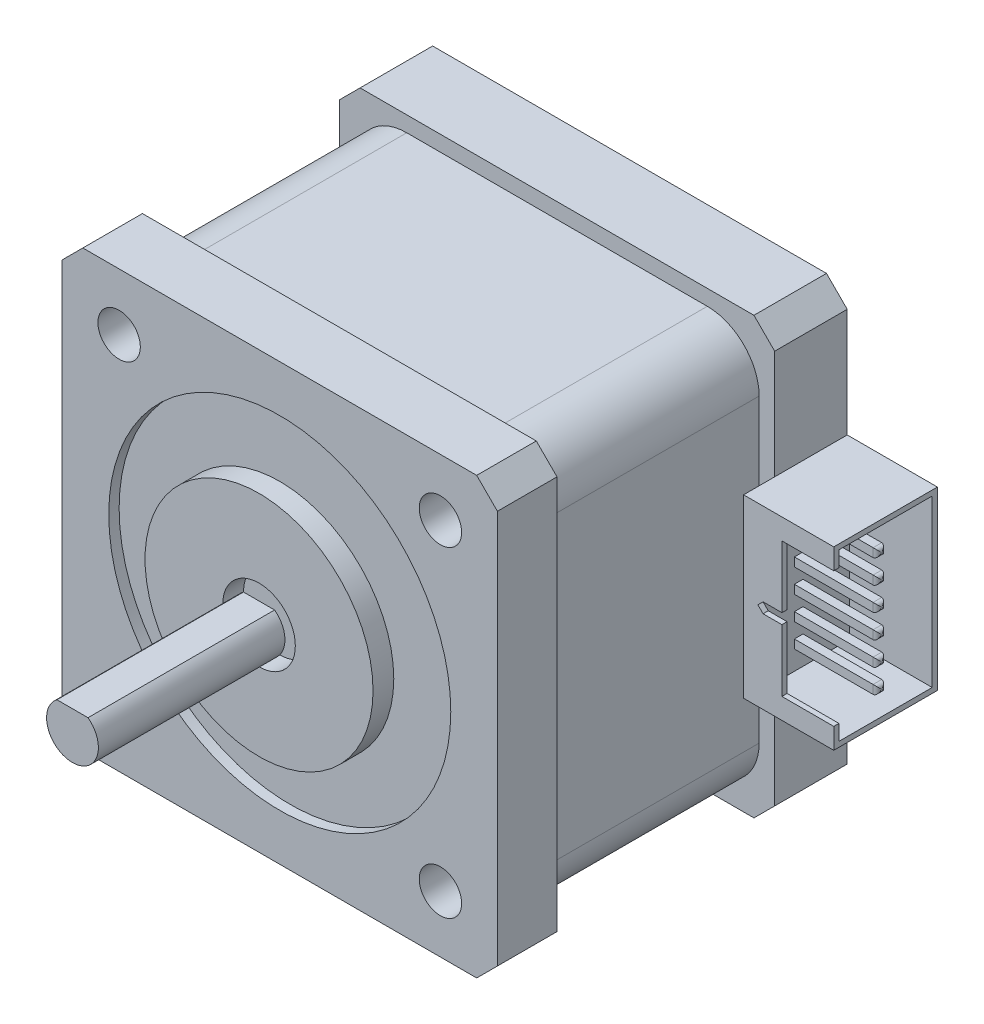
SolidWorks part; units mm, degrees
ref_plane "Alzado" through (0, 0, 0) normal (0, 0, 1) x (1, 0, 0)
ref_plane "Planta" through (0, 0, 0) normal (0, 1, 0) x (1, 0, 0)
ref_plane "Vista lateral" through (0, 0, 0) normal (1, 0, 0) x (0, 0, -1)
sketch "Croquis3" plane through (0, 0, 0) normal (0, 0, 1) x (1, 0, 0)
  line L0 (-1.5, 2) -> (1.5, 2)
  arc A0 (-1.5, 2) -> (1.5, 2) centre (0, 0) ccw
  dimension "D1" = 5
  dimension "D2" = 2
extrude "Saliente-Extruir1" add sketch "Croquis3" along normal blind 53.75
sketch "Croquis5" plane through (0, 0, 0) normal (0, 0, 1) x (1, 0, 0)
  line L1 (-21, 21) -> (21, 21)
  line L2 (-21, 21) -> (-21, -21)
  line L3 (-21, -21) -> (21, -21)
  line L4 (21, 21) -> (21, -21)
  line L5 (29.7, -8.5) -> (21, -8.5)
  line L6 (29.7, -8.5) -> (29.7, 8.5)
  line L7 (29.7, 8.5) -> (21, 8.5)
  line L8 (21, -8.5) -> (21, 8.5)
  dimension "D1" = 42
  dimension "D2" = 42
  dimension "D3" = 17
  dimension "D4" = 8.7
  dimension "D5" = 12.5
extrude "Saliente-Extruir2" add sketch "Croquis5" along normal blind 7 contours L4 L1 L2 L3 region at (0, 0, 0)
extrude "Saliente-Extruir3" add sketch "Croquis5<3>" along normal blind 10 contours L6 L7 L4 L5 region at (25.35, 0, 0)
sketch "Croquis5<3>" plane through (0, 0, 0) normal (0, 0, 1) x (1, 0, 0) same geometry as "Croquis5"
sketch "Croquis6" plane through (0, 0, 7) normal (0, 0, 1) x (1, 0, 0)
  line L1 (-19.5, 19.5) -> (19.5, 19.5)
  line L2 (-19.5, 19.5) -> (-19.5, -19.5)
  line L3 (-19.5, -19.5) -> (19.5, -19.5)
  line L4 (19.5, 19.5) -> (19.5, -19.5)
  point P4 (12.5866, -9.7505)
  point P5 (12.9433, -9.2154)
  point P8 (0, -19.5)
  point P9 (-19.5, 0)
  dimension "D1" = 39
extrude "Saliente-Extruir4" add sketch "Croquis6" along normal blind 21
sketch "Croquis7" plane through (0, 0, 28) normal (0, 0, 1) x (1, 0, 0)
  line L1 (-21, 21) -> (21, 21)
  line L2 (-21, 21) -> (-21, -21)
  line L3 (-21, -21) -> (21, -21)
  line L4 (21, 21) -> (21, -21)
extrude "Saliente-Extruir5" add sketch "Croquis7" along normal blind 5.75
sketch "Croquis8" plane through (0, 0, 33.75) normal (0, 0, 1) x (1, 0, 0)
  circle A0 centre (0, 0) radius 11
  dimension "D1" = 22
extrude "Saliente-Extruir6" add sketch "Croquis8" along normal blind 2
sketch "Croquis9" plane through (0, 0, 33.75) normal (0, 0, 1) x (1, 0, 0)
  circle A0 centre (0, 0) radius 16.5
  dimension "D1" = 33
extrude "Cortar-Extruir3" cut sketch "Croquis9" against normal blind 1
sketch "Croquis10" plane through (0, 0, 35.75) normal (0, 0, 1) x (1, 0, 0)
  circle A0 centre (0, 0) radius 3.5
  dimension "D1" = 7
extrude "Cortar-Extruir4" cut sketch "Croquis10" against normal blind 3
chamfer "Chaflán1" distance 2 angle 45 8 edges at (21, -21, 3.5) (21, -21, 30.875) (21, 21, 30.875) (21, 21, 3.5) (-21, 21, 30.875) (-21, 21, 3.5) (-21, -21, 3.5) (-21, -21, 30.875)
fillet "Redondeo1" radius 5 4 edges at (19.5, -19.5, 17.5) (-19.5, -19.5, 17.5) (-19.5, 19.5, 17.5) (19.5, 19.5, 17.5)
sketch "Croquis11" plane through (0, 0, 33.75) normal (0, 0, 1) x (1, 0, 0)
  line L0 (19, 21) -> (-19, 21) construction
  line L1 (-21, 19) -> (-21, -19) construction
  circle A0 centre (-15.5, 15.5) radius 2.0458
  circle A1 centre (15.5, 15.5) radius 2.0458
  circle A2 centre (15.5, -15.5) radius 2.0458
  circle A3 centre (-15.5, -15.5) radius 2.0458
  dimension "D1" = 5.5
  dimension "D2" = 5.5
  dimension "D3" = 2
  dimension "D4" = 2
sketch "Croquis12" plane through (0, 0, 0) normal (0, 0, 1) x (1, 0, 0)
  circle A0 centre (-15.5, 15.5) radius 2.0458
  circle A1 centre (15.5, 15.5) radius 2.0458
  circle A2 centre (15.5, -15.5) radius 2.0458
  circle A3 centre (-15.5, -15.5) radius 2.0458
  dimension "D3" = 2
  dimension "D4" = 2
extrude "Cortar-Extruir5" cut sketch "Croquis11" against normal blind 5
extrude "Cortar-Extruir6" cut sketch "Croquis12" along normal blind 5
sketch "Croquis13" plane through (29.7, 0, 0) normal (1, 0, 0) x (0, 0, -1)
  line L0 (-9.5, 8) -> (-9.5, -8)
  line L5 (-9.5, -8) -> (-0.5, -8)
  line L6 (-0.5, 8) -> (-0.5, -8)
  line L7 (-9.5, 8) -> (-0.5, 8)
extrude "Cortar-Extruir7" cut sketch "Croquis13" against normal blind 8
sketch "Croquis15" plane through (0, 0, 10) normal (0, 0, 1) x (1, 0, 0)
  line L0 (29.7, -6.5) -> (29.7, 6.5)
  line L1 (29.7, -8.5) -> (29.7, 8.5) construction
  line L2 (29.7, -8.5) -> (21, -8.5) construction
  line L3 (29.7, -6.5) -> (24.7, -6.5)
  line L4 (24.7, -6.5) -> (24.7, -0.5)
  line L5 (24.7, -0.5) -> (22.3815, -0.5)
  line L6 (22.3815, -0.5) -> (22.3815, 0)
  line L7 (22.3815, 0) -> (22.3815, 0.5)
  line L8 (22.3815, 0.5) -> (24.7, 0.5)
  line L9 (24.7, 0.5) -> (24.7, 6.5)
  line L10 (24.7, 6.5) -> (29.7, 6.5)
  point P7 (0, 0)
  dimension "D1" = 2
  dimension "D2" = 2
  dimension "D3" = 6
  dimension "D4" = 5
extrude "Cortar-Extruir9" cut sketch "Croquis15" against normal blind 0.5
chamfer "Chaflán2" distance 0.5 angle 45 2 edges at (22.3815, -0.5, 9.75) (22.3815, 0.5, 9.75)
sketch "Croquis16" plane through (21.7, 0, 0) normal (1, 0, 0) x (0, 0, -1)
  line L0 (-5.3837, 8) -> (-5.3837, 5.7143) construction
  line L1 (-0.5, 8) -> (-9.5, 8) construction
  line L2 (-5.3837, 5.7143) -> (-5.3837, 3.4286) construction
  line L3 (-5.3837, 3.4286) -> (-5.3837, 1.1429) construction
  line L4 (-5.3837, 1.1429) -> (-5.3837, -1.1429) construction
  line L5 (-5.3837, -1.1429) -> (-5.3837, -3.4286) construction
  line L6 (-5.3837, -3.4286) -> (-5.3837, -5.7143) construction
  line L7 (-5.3837, -5.7143) -> (-5.3837, -8) construction
  line L8 (-9.5, -8) -> (-0.5, -8) construction
  line L9 (-5.3837, 5.7143) -> (-5.3837, 6.1308) construction
  line L10 (-5.8003, 6.1308) -> (-4.9672, 6.1308)
  line L11 (-5.8003, 6.1308) -> (-5.8003, 5.2978)
  line L12 (-5.8003, 5.2978) -> (-4.9672, 5.2978)
  line L13 (-4.9672, 6.1308) -> (-4.9672, 5.2978)
  line L14 (-5.3837, 5.7143) -> (-5.8003, 5.7143) construction
  line L19 (-5.3837, -5.7143) -> (-5.3837, -5.2978) construction
  line L20 (-5.8003, -5.2978) -> (-4.9672, -5.2978)
  line L21 (-5.8003, -5.2978) -> (-5.8003, -6.1308)
  line L22 (-5.8003, -6.1308) -> (-4.9672, -6.1308)
  line L23 (-4.9672, -5.2978) -> (-4.9672, -6.1308)
  line L24 (-5.3837, -5.7143) -> (-5.8003, -5.7143) construction
  line L25 (-5.3837, -3.4286) -> (-5.3837, -3.0121) construction
  line L26 (-5.8003, -3.0121) -> (-4.9672, -3.0121)
  line L27 (-5.8003, -3.0121) -> (-5.8003, -3.8451)
  line L28 (-5.8003, -3.8451) -> (-4.9672, -3.8451)
  line L29 (-4.9672, -3.0121) -> (-4.9672, -3.8451)
  line L30 (-5.3837, -3.4286) -> (-5.8003, -3.4286) construction
  line L31 (-5.3837, -1.1429) -> (-5.3837, -0.7263) construction
  line L36 (-5.8003, -0.7263) -> (-4.9672, -0.7263)
  line L37 (-5.8003, -0.7263) -> (-5.8003, -1.5594)
  line L38 (-5.8003, -1.5594) -> (-4.9672, -1.5594)
  line L39 (-4.9672, -0.7263) -> (-4.9672, -1.5594)
  line L40 (-5.3837, -1.1429) -> (-5.8003, -1.1429) construction
  line L41 (-5.3837, 1.1429) -> (-5.3837, 1.5594) construction
  line L46 (-5.8003, 1.5594) -> (-4.9672, 1.5594)
  line L47 (-5.8003, 1.5594) -> (-5.8003, 0.7263)
  line L48 (-5.8003, 0.7263) -> (-4.9672, 0.7263)
  line L49 (-4.9672, 1.5594) -> (-4.9672, 0.7263)
  line L50 (-5.3837, 1.1429) -> (-5.8003, 1.1429) construction
  line L51 (-5.3837, 3.4286) -> (-5.3837, 3.8451) construction
  line L52 (-5.8003, 3.8451) -> (-4.9672, 3.8451)
  line L53 (-5.8003, 3.8451) -> (-5.8003, 3.0121)
  line L54 (-5.8003, 3.0121) -> (-4.9672, 3.0121)
  line L55 (-4.9672, 3.8451) -> (-4.9672, 3.0121)
  line L56 (-5.3837, 3.4286) -> (-5.8003, 3.4286) construction
  point P16 (-5.3837, 5.7143)
  point P19 (0, 0)
  point P25 (-5.3837, -5.7143)
  point P33 (-5.3837, -3.4286)
  point P41 (-5.3837, -1.1429)
  point P49 (-5.3837, 1.1429)
  point P57 (-5.3837, 3.4286)
  point P61 (0, 0)
  point P62 (0, 0)
  point P63 (0, 0)
  point P64 (0, 0)
  point P65 (0, 0)
  point P66 (0, 0)
extrude "Saliente-Extruir7" add sketch "Croquis16" along normal blind 8
fillet "Redondeo19" radius 0.4 24 edges at (29.7, 6.1308, 5.3837) (29.7, 5.7143, 4.9672) (29.7, 5.2978, 5.3837) (29.7, 5.7143, 5.8003) (29.7, 3.8451, 5.3837) (29.7, 3.4286, 4.9672) (29.7, 3.0121, 5.3837) (29.7, 3.4286, 5.8003) (29.7, 1.5594, 5.3837) (29.7, 1.1429, 4.9672) (29.7, 0.7263, 5.3837) (29.7, 1.1429, 5.8003) (29.7, -0.7263, 5.3837) (29.7, -1.1429, 4.9672) (29.7, -1.5594, 5.3837) (29.7, -1.1429, 5.8003) (29.7, -3.0121, 5.3837) (29.7, -3.4286, 4.9672) (29.7, -3.8451, 5.3837) (29.7, -3.4286, 5.8003) (29.7, -5.2978, 5.3837) (29.7, -5.7143, 4.9672) (29.7, -6.1308, 5.3837) (29.7, -5.7143, 5.8003)
